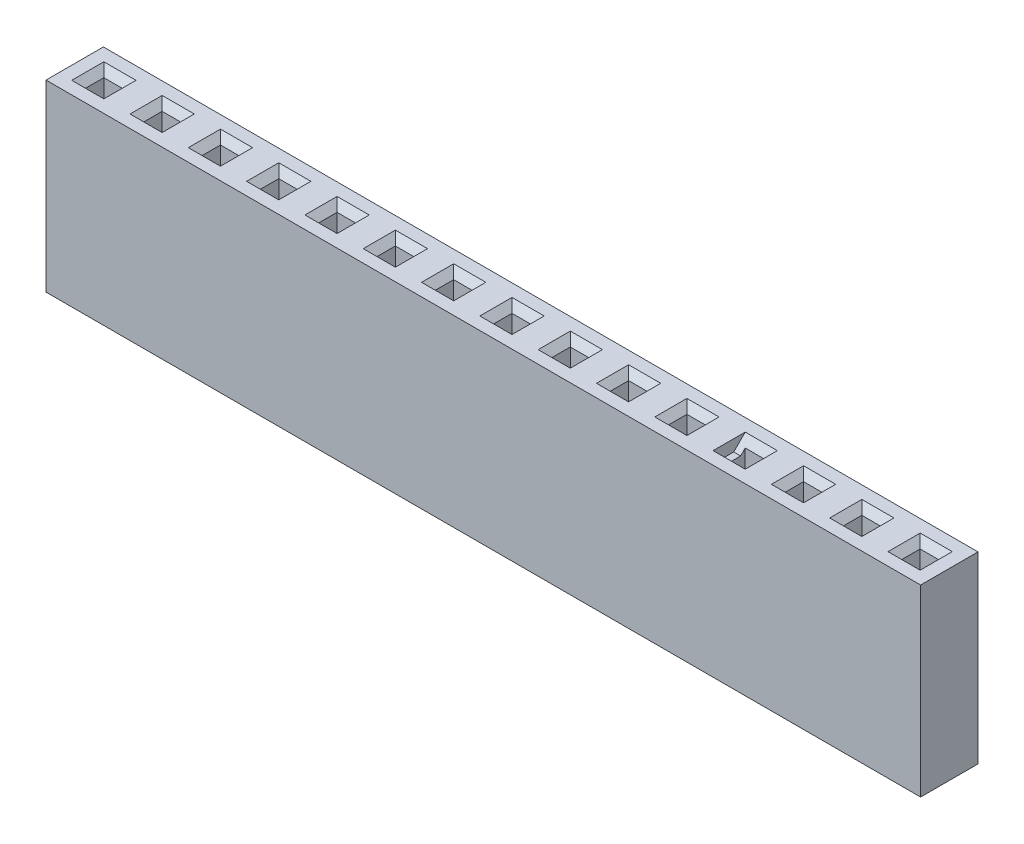
SolidWorks part; units mm, degrees
material "ABS"
ref_plane "Front Plane" through (0, 0, 0) normal (0, 0, 1) x (1, 0, 0)
ref_plane "Top Plane" through (0, 0, 0) normal (0, 1, 0) x (1, 0, 0)
ref_plane "Right Plane" through (0, 0, 0) normal (1, 0, 0) x (0, 0, -1)
sketch "Sketch1" plane through (0, 0, 0) normal (0, 1, 0) x (1, 0, 0)
  line L1 (0, 0) -> (-38.1, 0)
  line L2 (0, 0) -> (0, -2.5)
  line L3 (0, -2.5) -> (-38.1, -2.5)
  line L4 (-38.1, 0) -> (-38.1, -2.5)
  dimension "D1" = 38.1
  dimension "D2" = 2.5
extrude "Boss-Extrude1" add sketch "Sketch1" along normal blind 8
sketch "Sketch2" plane through (0, 8, 0) normal (0, 1, 0) x (1, 0, 0)
  line L0 (-34.69, -0.85) -> (-34.69, -1.65)
  line L1 (-37.23, -0.85) -> (-36.43, -0.85)
  line L2 (-37.23, -0.85) -> (-37.23, -1.65)
  line L3 (-37.23, -1.65) -> (-36.43, -1.65)
  line L4 (-36.43, -0.85) -> (-36.43, -1.65)
  line L5 (-34.69, -0.85) -> (-33.89, -0.85)
  line L6 (-34.69, -1.65) -> (-33.89, -1.65)
  line L7 (-33.89, -0.85) -> (-33.89, -1.65)
  line L8 (-32.15, -0.85) -> (-32.15, -1.65)
  line L9 (-32.15, -0.85) -> (-31.35, -0.85)
  line L10 (-32.15, -1.65) -> (-31.35, -1.65)
  line L11 (-31.35, -0.85) -> (-31.35, -1.65)
  line L12 (-29.61, -0.85) -> (-29.61, -1.65)
  line L13 (-29.61, -0.85) -> (-28.81, -0.85)
  line L14 (-29.61, -1.65) -> (-28.81, -1.65)
  line L15 (-28.81, -0.85) -> (-28.81, -1.65)
  line L16 (-27.07, -0.85) -> (-27.07, -1.65)
  line L17 (-27.07, -0.85) -> (-26.27, -0.85)
  line L18 (-27.07, -1.65) -> (-26.27, -1.65)
  line L19 (-26.27, -0.85) -> (-26.27, -1.65)
  line L20 (-24.53, -0.85) -> (-24.53, -1.65)
  line L21 (-24.53, -0.85) -> (-23.73, -0.85)
  line L22 (-24.53, -1.65) -> (-23.73, -1.65)
  line L23 (-23.73, -0.85) -> (-23.73, -1.65)
  line L24 (-21.99, -0.85) -> (-21.99, -1.65)
  line L25 (-21.99, -0.85) -> (-21.19, -0.85)
  line L26 (-21.99, -1.65) -> (-21.19, -1.65)
  line L27 (-21.19, -0.85) -> (-21.19, -1.65)
  line L28 (-19.45, -0.85) -> (-19.45, -1.65)
  line L29 (-19.45, -0.85) -> (-18.65, -0.85)
  line L30 (-19.45, -1.65) -> (-18.65, -1.65)
  line L31 (-18.65, -0.85) -> (-18.65, -1.65)
  line L32 (-16.91, -0.85) -> (-16.91, -1.65)
  line L33 (-16.91, -0.85) -> (-16.11, -0.85)
  line L34 (-16.91, -1.65) -> (-16.11, -1.65)
  line L35 (-16.11, -0.85) -> (-16.11, -1.65)
  line L36 (-14.37, -0.85) -> (-14.37, -1.65)
  line L37 (-14.37, -0.85) -> (-13.57, -0.85)
  line L38 (-14.37, -1.65) -> (-13.57, -1.65)
  line L39 (-13.57, -0.85) -> (-13.57, -1.65)
  line L40 (-11.83, -0.85) -> (-11.83, -1.65)
  line L41 (-11.83, -0.85) -> (-11.03, -0.85)
  line L42 (-11.83, -1.65) -> (-11.03, -1.65)
  line L43 (-11.03, -0.85) -> (-11.03, -1.65)
  line L44 (-9.29, -0.85) -> (-9.29, -1.65)
  line L45 (-9.29, -0.85) -> (-8.49, -0.85)
  line L46 (-9.29, -1.65) -> (-8.49, -1.65)
  line L47 (-8.49, -0.85) -> (-8.49, -1.65)
  line L48 (-6.75, -0.85) -> (-6.75, -1.65)
  line L49 (-6.75, -0.85) -> (-5.95, -0.85)
  line L50 (-6.75, -1.65) -> (-5.95, -1.65)
  line L51 (-5.95, -0.85) -> (-5.95, -1.65)
  line L52 (-4.21, -0.85) -> (-4.21, -1.65)
  line L53 (-4.21, -0.85) -> (-3.41, -0.85)
  line L54 (-4.21, -1.65) -> (-3.41, -1.65)
  line L55 (-3.41, -0.85) -> (-3.41, -1.65)
  line L56 (-1.67, -0.85) -> (-1.67, -1.65)
  line L57 (-1.67, -0.85) -> (-0.87, -0.85)
  line L58 (-1.67, -1.65) -> (-0.87, -1.65)
  line L59 (-0.87, -0.85) -> (-0.87, -1.65)
  line L60 (-38.1, 0) -> (-38.1, -2.5) construction
  point P4 (-37.23, -1.25)
  point P63 (-38.1, -1.25)
  point P64 (-36.83, -1.65)
  dimension "D1" = 0.8
  dimension "D2" = 15
  dimension "D3" = 1.27
extrude "Cut-Extrude1" cut sketch "Sketch2" against normal up to next
sketch "Sketch3" plane through (0, 8, 0) normal (0, 1, 0) x (1, 0, 0)
  line L8 (-34.99, -0.55) -> (-34.99, -1.95)
  line L9 (-33.59, -0.55) -> (-34.99, -0.55)
  line L10 (-33.59, -1.95) -> (-33.59, -0.55)
  line L11 (-34.99, -1.95) -> (-33.59, -1.95)
  line L12 (-36.13, -1.95) -> (-36.13, -0.55)
  line L13 (-36.13, -0.55) -> (-37.53, -0.55)
  line L14 (-37.53, -0.55) -> (-37.53, -1.95)
  line L15 (-37.53, -1.95) -> (-36.13, -1.95)
  line L16 (-36.13, -1.95) -> (-36.13, -0.55)
  line L17 (-36.13, -0.55) -> (-37.53, -0.55)
  line L18 (-37.53, -0.55) -> (-37.53, -1.95)
  line L19 (-37.53, -1.95) -> (-36.13, -1.95)
  line L20 (-32.45, -0.55) -> (-32.45, -1.95)
  line L21 (-31.05, -0.55) -> (-32.45, -0.55)
  line L22 (-31.05, -1.95) -> (-31.05, -0.55)
  line L23 (-32.45, -1.95) -> (-31.05, -1.95)
  line L24 (-29.91, -0.55) -> (-29.91, -1.95)
  line L25 (-28.51, -0.55) -> (-29.91, -0.55)
  line L26 (-28.51, -1.95) -> (-28.51, -0.55)
  line L27 (-29.91, -1.95) -> (-28.51, -1.95)
  line L28 (-27.37, -0.55) -> (-27.37, -1.95)
  line L29 (-25.97, -0.55) -> (-27.37, -0.55)
  line L30 (-25.97, -1.95) -> (-25.97, -0.55)
  line L31 (-27.37, -1.95) -> (-25.97, -1.95)
  line L32 (-24.83, -0.55) -> (-24.83, -1.95)
  line L33 (-23.43, -0.55) -> (-24.83, -0.55)
  line L34 (-23.43, -1.95) -> (-23.43, -0.55)
  line L35 (-24.83, -1.95) -> (-23.43, -1.95)
  line L36 (-22.29, -0.55) -> (-22.29, -1.95)
  line L37 (-20.89, -0.55) -> (-22.29, -0.55)
  line L38 (-20.89, -1.95) -> (-20.89, -0.55)
  line L39 (-22.29, -1.95) -> (-20.89, -1.95)
  line L40 (-19.75, -0.55) -> (-19.75, -1.95)
  line L41 (-18.35, -0.55) -> (-19.75, -0.55)
  line L42 (-18.35, -1.95) -> (-18.35, -0.55)
  line L43 (-19.75, -1.95) -> (-18.35, -1.95)
  line L44 (-17.21, -0.55) -> (-17.21, -1.95)
  line L45 (-15.81, -0.55) -> (-17.21, -0.55)
  line L46 (-15.81, -1.95) -> (-15.81, -0.55)
  line L47 (-17.21, -1.95) -> (-15.81, -1.95)
  line L48 (-14.67, -0.55) -> (-14.67, -1.95)
  line L49 (-13.27, -0.55) -> (-14.67, -0.55)
  line L50 (-13.27, -1.95) -> (-13.27, -0.55)
  line L51 (-14.67, -1.95) -> (-13.27, -1.95)
  line L52 (-12.13, -0.55) -> (-12.13, -1.95)
  line L53 (-10.73, -0.55) -> (-12.13, -0.55)
  line L54 (-10.73, -1.95) -> (-10.73, -0.55)
  line L55 (-12.13, -1.95) -> (-10.73, -1.95)
  line L56 (-9.59, -0.55) -> (-9.59, -1.95)
  line L57 (-8.19, -0.55) -> (-9.59, -0.55)
  line L58 (-8.19, -1.95) -> (-8.19, -0.55)
  line L59 (-9.59, -1.95) -> (-8.19, -1.95)
  line L60 (-7.05, -0.55) -> (-7.05, -1.95)
  line L61 (-5.65, -0.55) -> (-7.05, -0.55)
  line L62 (-5.65, -1.95) -> (-5.65, -0.55)
  line L63 (-7.05, -1.95) -> (-5.65, -1.95)
  line L64 (-4.51, -0.55) -> (-4.51, -1.95)
  line L65 (-3.11, -0.55) -> (-4.51, -0.55)
  line L66 (-3.11, -1.95) -> (-3.11, -0.55)
  line L67 (-4.51, -1.95) -> (-3.11, -1.95)
  line L68 (-1.97, -0.55) -> (-1.97, -1.95)
  line L69 (-0.57, -0.55) -> (-1.97, -0.55)
  line L70 (-0.57, -1.95) -> (-0.57, -0.55)
  line L71 (-1.97, -1.95) -> (-0.57, -1.95)
  dimension "D1" = 0.3
  dimension "D2" = 15
extrude "Cut-Extrude2" cut sketch "Sketch3" against normal blind 0.5
chamfer "Chamfer1" distance 0.5 angle 45 59 edges at (-0.57, 7.5, 1.25) (-1.27, 7.5, 0.55) (-1.97, 7.5, 1.25) (-1.27, 7.5, 1.95) (-3.11, 7.5, 1.25) (-3.81, 7.5, 0.55) (-4.51, 7.5, 1.25) (-3.81, 7.5, 1.95) (-5.65, 7.5, 1.25) (-6.35, 7.5, 0.55) (-7.05, 7.5, 1.25) (-6.35, 7.5, 1.95) (-8.89, 7.5, 0.55) (-8.19, 7.5, 1.25) (-8.89, 7.5, 1.95) (-10.73, 7.5, 1.25) (-11.43, 7.5, 0.55) (-12.13, 7.5, 1.25) (-11.43, 7.5, 1.95) (-13.27, 7.5, 1.25) (-13.97, 7.5, 0.55) (-14.67, 7.5, 1.25) (-13.97, 7.5, 1.95) (-15.81, 7.5, 1.25) (-16.51, 7.5, 0.55) (-17.21, 7.5, 1.25) (-16.51, 7.5, 1.95) (-18.35, 7.5, 1.25) (-19.05, 7.5, 0.55) (-19.75, 7.5, 1.25) (-19.05, 7.5, 1.95) (-20.89, 7.5, 1.25) (-21.59, 7.5, 0.55) (-22.29, 7.5, 1.25) (-21.59, 7.5, 1.95) (-23.43, 7.5, 1.25) (-24.13, 7.5, 0.55) (-24.83, 7.5, 1.25) (-24.13, 7.5, 1.95) (-25.97, 7.5, 1.25) (-26.67, 7.5, 0.55) (-27.37, 7.5, 1.25) (-26.67, 7.5, 1.95) (-28.51, 7.5, 1.25) (-29.21, 7.5, 0.55) (-29.91, 7.5, 1.25) (-29.21, 7.5, 1.95) (-31.05, 7.5, 1.25) (-31.75, 7.5, 0.55) (-32.45, 7.5, 1.25) (-31.75, 7.5, 1.95) (-33.59, 7.5, 1.25) (-34.29, 7.5, 0.55) (-34.99, 7.5, 1.25) (-34.29, 7.5, 1.95) (-37.53, 7.5, 1.25) (-36.83, 7.5, 1.95) (-36.13, 7.5, 1.25) (-36.83, 7.5, 0.55)
sketch "Sketch4" plane through (0, 0, 0) normal (0, -1, 0) x (1, 0, 0)
  line L10 (-35.19, 2.15) -> (-35.19, 0.35)
  line L11 (-33.39, 2.15) -> (-35.19, 2.15)
  line L12 (-33.39, 0.35) -> (-33.39, 2.15)
  line L13 (-35.19, 0.35) -> (-33.39, 0.35)
  line L14 (-37.73, 0.35) -> (-35.93, 0.35)
  line L15 (-35.93, 0.35) -> (-35.93, 2.15)
  line L16 (-35.93, 2.15) -> (-37.73, 2.15)
  line L17 (-37.73, 2.15) -> (-37.73, 0.35)
  line L18 (-37.73, 0.35) -> (-35.93, 0.35)
  line L19 (-35.93, 0.35) -> (-35.93, 2.15)
  line L20 (-35.93, 2.15) -> (-37.73, 2.15)
  line L21 (-37.73, 2.15) -> (-37.73, 0.35)
  line L22 (-32.65, 2.15) -> (-32.65, 0.35)
  line L23 (-30.85, 2.15) -> (-32.65, 2.15)
  line L24 (-30.85, 0.35) -> (-30.85, 2.15)
  line L25 (-32.65, 0.35) -> (-30.85, 0.35)
  line L26 (-30.11, 2.15) -> (-30.11, 0.35)
  line L27 (-28.31, 2.15) -> (-30.11, 2.15)
  line L28 (-28.31, 0.35) -> (-28.31, 2.15)
  line L29 (-30.11, 0.35) -> (-28.31, 0.35)
  line L30 (-27.57, 2.15) -> (-27.57, 0.35)
  line L31 (-25.77, 2.15) -> (-27.57, 2.15)
  line L32 (-25.77, 0.35) -> (-25.77, 2.15)
  line L33 (-27.57, 0.35) -> (-25.77, 0.35)
  line L34 (-25.03, 2.15) -> (-25.03, 0.35)
  line L35 (-23.23, 2.15) -> (-25.03, 2.15)
  line L36 (-23.23, 0.35) -> (-23.23, 2.15)
  line L37 (-25.03, 0.35) -> (-23.23, 0.35)
  line L38 (-22.49, 2.15) -> (-22.49, 0.35)
  line L39 (-20.69, 2.15) -> (-22.49, 2.15)
  line L40 (-20.69, 0.35) -> (-20.69, 2.15)
  line L41 (-22.49, 0.35) -> (-20.69, 0.35)
  line L42 (-19.95, 2.15) -> (-19.95, 0.35)
  line L43 (-18.15, 2.15) -> (-19.95, 2.15)
  line L44 (-18.15, 0.35) -> (-18.15, 2.15)
  line L45 (-19.95, 0.35) -> (-18.15, 0.35)
  line L46 (-17.41, 2.15) -> (-17.41, 0.35)
  line L47 (-15.61, 2.15) -> (-17.41, 2.15)
  line L48 (-15.61, 0.35) -> (-15.61, 2.15)
  line L49 (-17.41, 0.35) -> (-15.61, 0.35)
  line L50 (-14.87, 2.15) -> (-14.87, 0.35)
  line L51 (-13.07, 2.15) -> (-14.87, 2.15)
  line L52 (-13.07, 0.35) -> (-13.07, 2.15)
  line L53 (-14.87, 0.35) -> (-13.07, 0.35)
  line L54 (-12.33, 2.15) -> (-12.33, 0.35)
  line L55 (-10.53, 2.15) -> (-12.33, 2.15)
  line L56 (-10.53, 0.35) -> (-10.53, 2.15)
  line L57 (-12.33, 0.35) -> (-10.53, 0.35)
  line L58 (-9.79, 2.15) -> (-9.79, 0.35)
  line L59 (-7.99, 2.15) -> (-9.79, 2.15)
  line L60 (-7.99, 0.35) -> (-7.99, 2.15)
  line L61 (-9.79, 0.35) -> (-7.99, 0.35)
  line L62 (-7.25, 2.15) -> (-7.25, 0.35)
  line L63 (-5.45, 2.15) -> (-7.25, 2.15)
  line L64 (-5.45, 0.35) -> (-5.45, 2.15)
  line L65 (-7.25, 0.35) -> (-5.45, 0.35)
  line L66 (-4.71, 2.15) -> (-4.71, 0.35)
  line L67 (-2.91, 2.15) -> (-4.71, 2.15)
  line L68 (-2.91, 0.35) -> (-2.91, 2.15)
  line L69 (-4.71, 0.35) -> (-2.91, 0.35)
  line L70 (-2.17, 2.15) -> (-2.17, 0.35)
  line L71 (-0.37, 2.15) -> (-2.17, 2.15)
  line L72 (-0.37, 0.35) -> (-0.37, 2.15)
  line L73 (-2.17, 0.35) -> (-0.37, 0.35)
  dimension "D1" = 0.5
  dimension "D2" = 15
extrude "Cut-Extrude3" cut sketch "Sketch4" against normal blind 6.5
